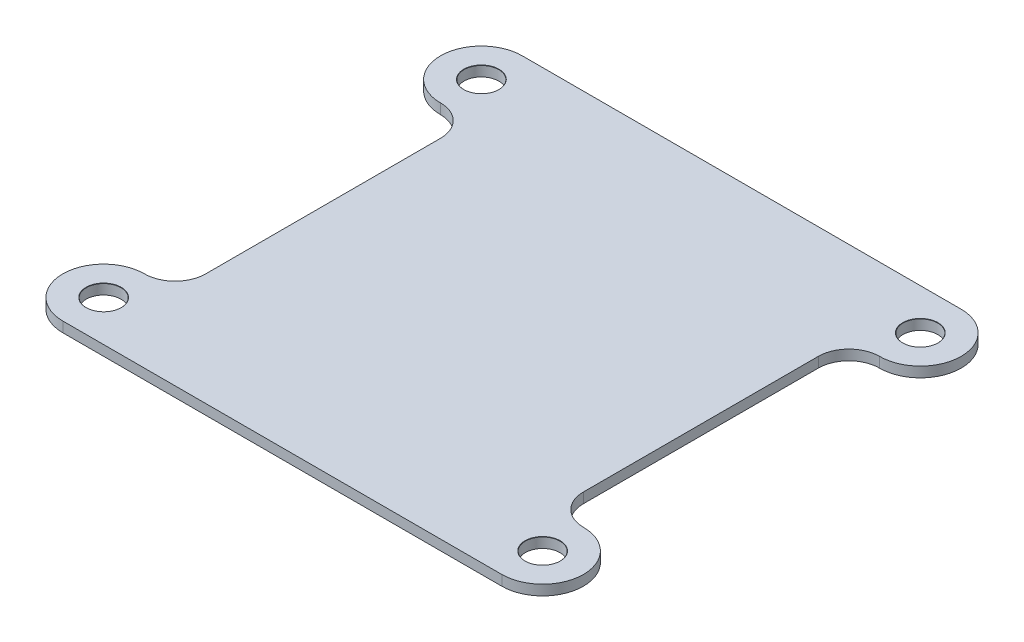
SolidWorks part; units mm, degrees
ref_plane "Front Plane" through (0, 0, 0) normal (0, 0, 1) x (1, 0, 0)
ref_plane "Top Plane" through (0, 0, 0) normal (0, 1, 0) x (1, 0, 0)
ref_plane "Right Plane" through (0, 0, 0) normal (1, 0, 0) x (0, 0, -1)
sketch "Sketch1" plane through (0, 0, 0) normal (0, 1, 0) x (1, 0, 0)
  line L1 (18.5, -22.5) -> (-18.5, -22.5)
  line L2 (18.5, -22.5) -> (18.5, 22.5)
  line L3 (18.5, 22.5) -> (-18.5, 22.5)
  line L4 (-18.5, -22.5) -> (-18.5, 22.5)
  line L5 (18.5, -22.5) -> (-18.5, 22.5) construction
  line L6 (18.5, 22.5) -> (-18.5, -22.5) construction
  point P0 (0, 0)
  dimension "D1" = 45
  dimension "D2" = 37
extrude "Boss-Extrude1" add sketch "Sketch1" along normal blind 1
sketch "Sketch2" plane through (0, 0, 0) normal (0, -1, 0) x (1, 0, 0)
  line L0 (21.5, 18.5) -> (-21.5, 18.5) construction
  line L1 (21.5, 14.5) -> (-21.5, 14.5)
  line L2 (21.5, 22.5) -> (-21.5, 22.5)
  line L3 (55, 0) -> (-55, 0) construction
  line L4 (21.5, -18.5) -> (-21.5, -18.5) construction
  line L5 (21.5, -14.5) -> (-21.5, -14.5)
  line L6 (21.5, -22.5) -> (-21.5, -22.5)
  line L7 (-18.5, 22.5) -> (18.5, 22.5) construction
  line L8 (-18.5, -22.5) -> (-18.5, 22.5) construction
  arc A0 (21.5, 14.5) -> (21.5, 22.5) centre (21.5, 18.5) ccw
  arc A1 (-21.5, 22.5) -> (-21.5, 14.5) centre (-21.5, 18.5) ccw
  arc A2 (21.5, -14.5) -> (21.5, -22.5) centre (21.5, -18.5) cw
  arc A3 (-21.5, -22.5) -> (-21.5, -14.5) centre (-21.5, -18.5) cw
  point P2 (0, 18.5)
  point P11 (0, -18.5)
  dimension "D1" = 4
  dimension "D2" = 3
extrude "Boss-Extrude2" add sketch "Sketch2" against normal up to surface (1 mm away) up to face at (0, 1, 0)
fillet "Fillet1" radius 3 4 edges at (-18.5, 0.5, 14.5) (-18.5, 0.5, -14.5) (18.5, 0.5, -14.5) (18.5, 0.5, 14.5)
hole_wizard "M3 Clearance Hole1" positions "Sketch3" profile "Sketch5" hole size "M3" standard "GB" end condition through all
sketch "Sketch3" plane through (0, 1, 0) normal (0, 1, 0) x (1, 0, 0)
  line L0 (-55, 0) -> (55, 0) construction
  line L1 (0, -55) -> (0, 55) construction
  point P0 (-21.5, 18.5)
  point P6 (-21.5, -18.5)
  point P9 (21.5, -18.5)
  point P10 (21.5, 18.5)
sketch "Sketch5" plane through (-21.5, 1, -18.5) normal (1, 0, 0) x (0, 0, 1)
  line L0 (0, 0) -> (0, 1)
  line L1 (0, 1) -> (1.7, 1)
  line L2 (1.7, 1) -> (1.7, 0.025)
  line L3 (1.7, 0.025) -> (1.725, 0)
  line L5 (1.725, 0) -> (0, 0)
  line L6 (-1.7, 0.025) -> (-1.725, 0) construction
  line L11 (0, -6.35) -> (0, 107.95) construction
  dimension "Thru Hole Dia." = 3.4
  dimension "Thru Hole Depth" = 1
  dimension "Near C'Sink Dia." = 3.45
  dimension "Near C'Sink Angle" = 90
